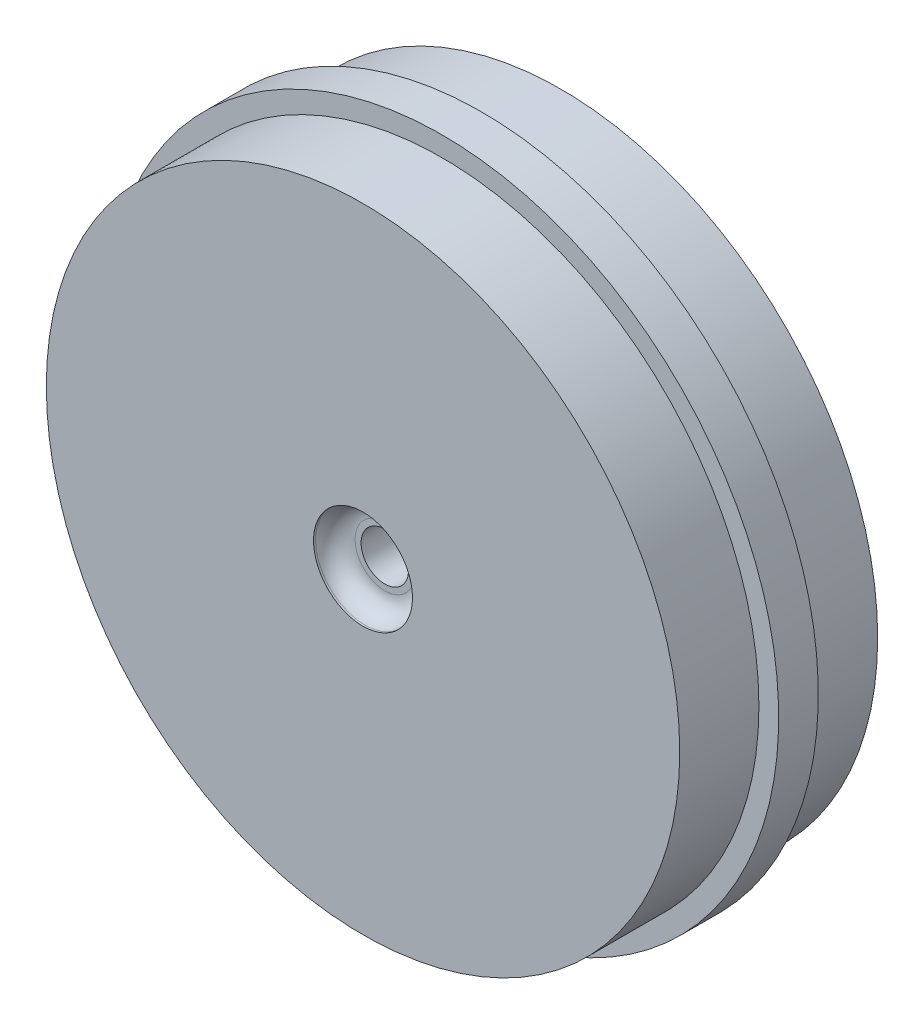
SolidWorks part; units mm, degrees
material "PET"
ref_plane "Plan de face" through (0, 0, 0) normal (0, 0, 1) x (1, 0, 0)
ref_plane "Plan de dessus" through (0, 0, 0) normal (0, 1, 0) x (1, 0, 0)
ref_plane "Plan de droite" through (0, 0, 0) normal (1, 0, 0) x (0, 0, -1)
sketch "Esquisse1" plane through (0, 0, 0) normal (0, 0, 1) x (1, 0, 0)
  circle A0 centre (0, 0) radius 14.5
  dimension "D1" = 29
extrude "Boss.-Extru.1" add sketch "Esquisse1" along normal blind 10
sketch "Esquisse2" plane through (0, 0, 0) normal (0, 0, 1) x (1, 0, 0)
  circle A0 centre (0, 0) radius 16.5
  dimension "D1" = 33
extrude "Boss.-Extru.2" add sketch "Esquisse2" along normal offset from surface (8 mm away) 1 from offset 1 up to face at (14.5, 0, 10)
sketch "Esquisse6" plane through (0, 0, 10) normal (0, 0, 1) x (1, 0, 0)
  circle A0 centre (0, 0) radius 13.5
  dimension "D1" = 27
extrude "Enlèv. mat.-Extru.4" cut sketch "Esquisse6" against normal blind 1
hole_wizard "Chambrage pour vis à tête ronde bombée M21" positions "Esquisse9" profile "Esquisse8" counterbore size "M2" standard "Ansi Metric" end condition through all
sketch "Esquisse9" plane through (0, 0, 9) normal (0, 0, 1) x (1, 0, 0)
  point P0 (0, 0)
sketch "Esquisse8" plane through (0, 0, 9) normal (1, 0, 0) x (0, -1, 0)
  line L0 (0, 0) -> (0, 9)
  line L1 (0, 9) -> (1.2, 9)
  line L3 (1.2, 9) -> (1.2, 1.6)
  line L4 (1.2, 1.6) -> (2.5, 1.6)
  line L5 (2.5, 1.6) -> (2.5, 0)
  line L7 (2.5, 0) -> (0, 0)
  line L11 (0, -6.35) -> (0, 107.95) construction
  dimension "Diamètre du perçage jusqu'au prochain" = 2.4
  dimension "Profondeur du perçage jusqu'au prochain" = 9
  dimension "Diamètre du chambrage" = 5
  dimension "Profondeur du chambrage" = 1.6
sketch "Esquisse13" plane through (0, 0, 0) normal (0, 0, -1) x (-1, 0, 0)
  circle A0 centre (0, 0) radius 13.5
  circle A1 centre (0, 0) radius 4.2
  dimension "D1" = 27
  dimension "D2" = 8.4
extrude "Enlèv. mat.-Extru.7" cut sketch "Esquisse13" against normal offset from surface (7 mm away) 2 up to face at (2.5, 0, 9)
sketch "Esquisse15" plane through (0, 0, 0) normal (0, 0, -1) x (-1, 0, 0)
  line L0 (-1.9, 1.9881) -> (-1.9, -1.9881)
  line L1 (1.9, 1.9881) -> (1.9, -1.9881)
  arc A0 (-1.9, -1.9881) -> (1.9, -1.9881) centre (0, 0) ccw
  arc A1 (1.9, 1.9881) -> (-1.9, 1.9881) centre (0, 0) ccw
  dimension "D1" = 5.5
  dimension "D2" = 1.9
  dimension "D3" = 1.9
extrude "Enlèv. mat.-Extru.8" cut sketch "Esquisse15" against normal blind 7
sketch "Sketch2" plane through (0, 0, 1) normal (0, 0, -1) x (-1, 0, 0)
  circle A0 centre (0, 0) radius 16.5
  circle A1 centre (0, 0) radius 14.5
extrude "Boss-Extrude2" add sketch "Sketch2" along normal up to surface (1 mm away) and the other way up to surface (9 mm away) up to face at (0, 0, 0) other way up to face at (13.5, 0, 10)
sketch "Sketch3" plane through (0, 0, 0) normal (0, 0, -1) x (-1, 0, 0)
  circle A0 centre (0, 0) radius 16.5
  circle A1 centre (0, 0) radius 22.5
  dimension "D1" = 6
extrude "Boss-Extrude3" add sketch "Sketch3" against normal up to surface (10 mm away) up to face at (13.5, 0, 10)
fillet "Fillet1" radius 1 2 edges at (-22.5, 0, 0) (22.5, 0, 10)
ref_plane "Plane1" through (0, 0, 0) normal (1, 0, 0) x (0, 0, -1)
sketch "Sketch4" plane through (0, 0, 0) normal (1, 0, 0) x (0, 0, -1)
  line L0 (-9, 22.5) -> (-1, 22.5) construction
  line L1 (-1, 22.5) -> (-9, 22.5) construction
  line L2 (-9, 22.5) -> (-9, 18)
  line L3 (-5, 22.5) -> (-5, 24.473) construction
  line L4 (-9, 18) -> (-1, 18)
  line L5 (-1, 18) -> (-1, 22.5)
  arc A0 (-9, 22.5) -> (-1, 22.5) centre (-5, 14.0611) cw
  point P10 (-5, 23.4)
  dimension "D2" = 0.9
extrude "Boss-Extrude4" add sketch "Sketch4" along normal blind 0.5 and the other way blind 0.5
pattern_circular "CirPattern1" count 70 over 360 about axis through (0, 0, 73.6396) along (0, 0, -1) of "Boss-Extrude4"
sketch "Sketch5" plane through (0, 0, 0) normal (0, 0, -1) x (-1, 0, 0)
  circle A0 centre (0, 0) radius 16
  circle A1 centre (0, 0) radius 40
  dimension "D1" = 32
  dimension "D2" = 80
extrude "Cut-Extrude1" cut sketch "Sketch5" against normal blind 20
sketch "Sketch6" plane through (0, 0, 0) normal (0, 0, -1) x (-1, 0, 0)
  circle A0 centre (0, 0) radius 16
  circle A1 centre (0, 0) radius 17
  circle A2 centre (0, 0) radius 16 construction
  dimension "D1" = 1
extrude "Boss-Extrude5" add sketch "Sketch6" against normal blind 2 from offset 4 offset against normal yes
sketch "Sketch8" plane through (0, 0, 9) normal (0, 0, 1) x (1, 0, 0)
  circle A0 centre (0, 0) radius 13.5
  circle A1 centre (0, 0) radius 2.5
  circle A2 centre (0, 0) radius 13.5 construction
  circle A3 centre (0, 0) radius 2.5 construction
extrude "Boss-Extrude6" add sketch "Sketch8" along normal up to surface (1 mm away) up to face at (13.5, 0, 10)
sketch "Sketch9" plane through (0, 0, 7.4) normal (0, 0, 1) x (1, 0, 0)
  circle A0 centre (0, 0) radius 2.5
  circle A1 centre (0, 0) radius 1.2
  circle A2 centre (0, 0) radius 1.2 construction
  circle A3 centre (0, 0) radius 2.5 construction
extrude "Boss-Extrude7" add sketch "Sketch9" along normal blind 1.5
fillet "Fillet2" radius 1 1 edges at (2.5, 0, 8.9)
